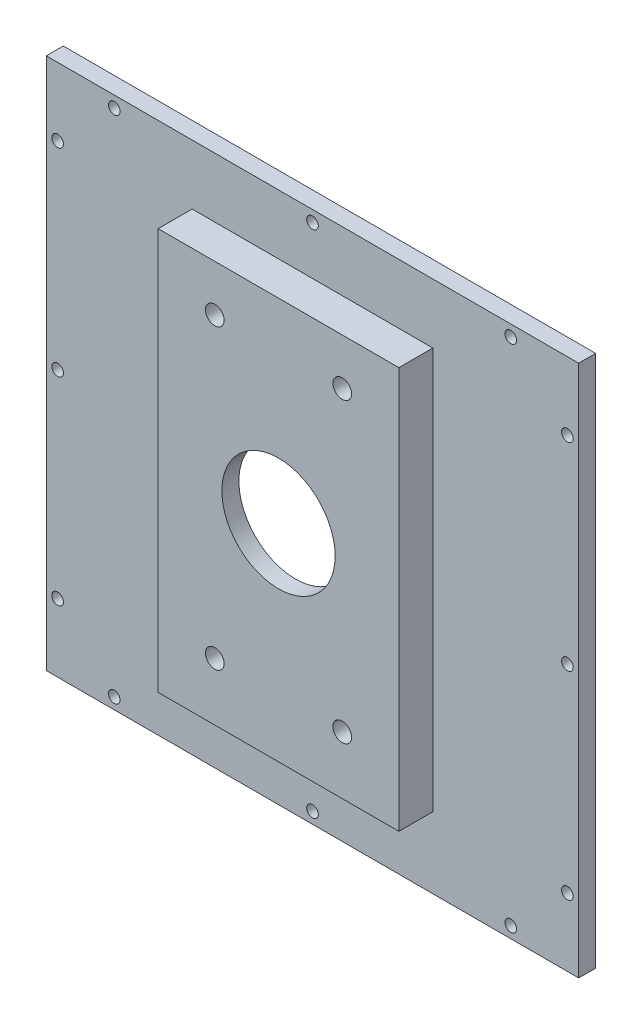
SolidWorks part; units mm, degrees
ref_plane "前视基准面" through (0, 0, 0) normal (0, 0, 1) x (1, 0, 0)
ref_plane "上视基准面" through (0, 0, 0) normal (0, 1, 0) x (1, 0, 0)
ref_plane "右视基准面" through (0, 0, 0) normal (1, 0, 0) x (0, 0, -1)
sketch "草图1" plane through (0, 0, 0) normal (0, 0, 1) x (1, 0, 0)
  line L0 (47, -49) -> (47, 45)
  line L1 (47, 45) -> (43, 45)
  line L2 (43, 45) -> (43, -49)
  line L3 (43, -49) -> (47, -49)
  line L4 (-43, -49) -> (43, -49)
  line L5 (43, -49) -> (43, -45)
  line L6 (43, -45) -> (-43, -45)
  line L7 (-43, -45) -> (-43, -49)
  line L8 (-43, -49) -> (-43, 45)
  line L9 (-43, 45) -> (-47, 45)
  line L10 (-47, 45) -> (-47, -49)
  line L11 (-47, -49) -> (-43, -49)
  line L12 (-43, 41) -> (43, 41)
  line L13 (43, 41) -> (43, 45)
  line L14 (43, 45) -> (26.5, 45)
  line L15 (26.5, 45) -> (-26.5, 45)
  line L16 (11.25, -36.45) -> (-11.25, -36.45)
  line L17 (11.25, 34.45) -> (-11.25, 34.45)
  line L18 (0, 45) -> (0, -49) construction
  line L19 (-11.25, 34.45) -> (-21.25, 34.45)
  line L20 (21.25, -36.45) -> (21.25, 34.45)
  line L21 (-11.25, -36.45) -> (-21.25, -36.45)
  line L22 (-26.5, 45) -> (-43, 45)
  line L23 (-43, 45) -> (-43, 41)
  line L24 (-21.25, -36.45) -> (-21.25, 34.45)
  line L25 (11.25, -36.45) -> (21.25, -36.45)
  line L26 (11.25, 34.45) -> (21.25, 34.45)
  line L27 (-10, 0) -> (10, 0) construction
  line L28 (-21.25, -30.45) -> (21.25, -30.45)
  line L29 (-21.25, 30.45) -> (21.25, 30.45)
  line L30 (-16.25, -36.45) -> (-16.25, 34.45)
  line L31 (16.25, 34.45) -> (16.25, -36.45)
  circle A0 centre (11.25, 26.25) radius 1.65
  circle A1 centre (11.25, -26.25) radius 1.65
  circle A2 centre (0, 0) radius 10
  circle A9 centre (-11.25, -26.25) radius 1.65
  circle A11 centre (11.25, -26.25) radius 1.65
  circle A13 centre (11.25, 26.25) radius 1.65
  circle A15 centre (-11.25, 26.25) radius 1.65
extrude "凸台-拉伸1" add sketch "草图1" along normal blind 3 contours L18 L12 L8 L6 L16 L21 L24 L19 L17 | L12 L18 L17 L26 L20 L25 L16 L6 L2 | L18 L15 L22 L8 L12 | L15 L18 L12 L2 L14 | L2 L3 L0 L1 | L10 L11 L7 L8 L9 | L18 L6 L7 L4 | L6 L18 L4 L2 region at (45, -2, 0) region at (0, -47, 0) region at (0, 43, 0) region at (0, -43.7838, 0) region at (-45, -2, 0)
extrude "凸台-拉伸2" add sketch "草图1<5>" along normal blind 6 contours L24 L20 L26 L17 L19 | L24 L21 L16 L25 L20 | L26 L31 L20 | L31 L20 | L31 L25 L20 | L21 L30 L24 | L30 L24 | L30 L19 L24 region at (0, -33.45, 0) region at (18.75, -33.45, 0) region at (-18.75, -33.45, 0) region at (18.75, 0, 0) region at (-18.75, 0, 0) region at (18.75, 32.45, 0) region at (0, 32.45, 0) region at (-18.75, 32.45, 0)
sketch "草图1<5>" plane through (0, 0, 0) normal (0, 0, 1) x (1, 0, 0) same geometry as "草图1"
ref_plane "基准面1" through (0, 0, 6) normal (0, 0, 1) x (1, 0, 0)
sketch "草图2" plane through (0, 0, 6) normal (0, 0, 1) x (1, 0, 0)
  line L16 (11.25, -36.45) -> (-11.25, -36.45)
  line L17 (11.25, 34.45) -> (-11.25, 34.45)
  line L18 (0, 45) -> (0, -49) construction
  line L19 (-11.25, 34.45) -> (-21.25, 34.45)
  line L20 (21.25, -36.45) -> (21.25, 34.45)
  line L21 (-11.25, -36.45) -> (-21.25, -36.45)
  line L24 (-21.25, -36.45) -> (-21.25, 34.45)
  line L25 (11.25, -36.45) -> (21.25, -36.45)
  line L26 (11.25, 34.45) -> (21.25, 34.45)
  circle A0 centre (11.25, 26.25) radius 1.65
  circle A1 centre (11.25, -26.25) radius 1.65
  circle A2 centre (0, 0) radius 10
  circle A9 centre (-11.25, -26.25) radius 1.65
  circle A11 centre (11.25, -26.25) radius 1.65
  circle A13 centre (11.25, 26.25) radius 1.65
  circle A15 centre (-11.25, 26.25) radius 1.65
extrude "凸台-拉伸3" add sketch "草图2" along normal blind 3 contours L18 L17 L19 L24 L21 L16 A2 A15 A9 | L17 L18 A2 L16 L25 L20 L26 A1 A0 | A0 | A15 | A1 | A9 region at (11.3692, -1.1307, 6) region at (-11.3692, -1.1307, 6) region at (11.25, 26.25, 6) region at (11.25, -26.25, 6) region at (-11.25, -26.25, 6) region at (-11.25, 26.25, 6)
hole_wizard "M4 螺纹孔1" positions "草图5" profile "草图6" tap size "M4" standard "GB"
sketch "草图5" plane through (0, 0, 9) normal (0, 0, 1) x (1, 0, 0)
  point P0 (11.25, 26.25)
  point P3 (-11.25, 26.25)
  point P6 (-11.25, -26.25)
  point P9 (11.25, -26.25)
sketch "草图6" plane through (11.25, 26.25, 9) normal (1, 0, 0) x (0, -1, 0)
  line L0 (0, 0) -> (0, 12.4914)
  line L1 (0, 12.4914) -> (1.65, 11.5)
  line L2 (1.65, 11.5) -> (1.65, 0)
  line L5 (1.65, 0) -> (0, 0)
  line L10 (0, 12.4914) -> (-1.65, 11.5) construction
  line L11 (0, -6.35) -> (0, 107.95) construction
  dimension "螺纹孔钻头直径" = 3.3
  dimension "螺纹孔钻头深度" = 11.5
  dimension "导头角度" = 118
cosmetic thread "孔螺蚊线1" parameters "D1"=3, "D2"=4
cosmetic thread "孔螺蚊线2" parameters "D1"=3, "D2"=4
cosmetic thread "孔螺蚊线3" parameters "D1"=3, "D2"=4
cosmetic thread "孔螺蚊线4" parameters "D1"=3, "D2"=4
sketch "草图7" plane through (0, 0, 0) normal (0, 0, 1) x (1, 0, 0)
  circle A0 centre (-45, -2) radius 1.25
  circle A1 centre (-45, 33) radius 1.25
  circle A2 centre (-45, -37) radius 1.25
  circle A3 centre (45, -2) radius 1.25
  circle A4 centre (45, 33) radius 1.25
  circle A5 centre (45, -37) radius 1.25
  circle A6 centre (0, -47) radius 1.25
  circle A7 centre (-35, -47) radius 1.25
  circle A8 centre (35, -47) radius 1.25
  circle A9 centre (0, 43) radius 1.25
  circle A10 centre (-35, 43) radius 1.25
  circle A11 centre (35, 43) radius 1.25
  dimension "D1" = 2
  dimension "D2" = 2
hole_wizard "M2.5 螺纹孔1" positions "草图8" profile "草图9" tap size "M2.5" standard "GB"
sketch "草图8" plane through (0, 0, 3) normal (0, 0, 1) x (1, 0, 0)
  point P0 (-45, 33)
  point P3 (-45, -2)
  point P6 (-45, -37)
  point P10 (-35, 43)
  point P13 (0, 43)
  point P16 (35, 43)
  point P19 (45, 33)
sketch "草图9" plane through (-45, 33, 3) normal (1, 0, 0) x (0, -1, 0)
  line L0 (0, 0) -> (0, 7.8659)
  line L1 (0, 7.8659) -> (1.025, 7.25)
  line L2 (1.025, 7.25) -> (1.025, 0)
  line L5 (1.025, 0) -> (0, 0)
  line L10 (0, 7.8659) -> (-1.025, 7.25) construction
  line L11 (0, -6.35) -> (0, 107.95) construction
  dimension "螺纹孔钻头直径" = 2.05
  dimension "螺纹孔钻头深度" = 7.25
  dimension "导头角度" = 118
cosmetic thread "孔螺蚊线5" parameters "D1"=3, "D2"=2.5
cosmetic thread "孔螺蚊线6" parameters "D1"=3, "D2"=2.5
cosmetic thread "孔螺蚊线7" parameters "D1"=3, "D2"=2.5
cosmetic thread "孔螺蚊线8" parameters "D1"=3, "D2"=2.5
cosmetic thread "孔螺蚊线9" parameters "D1"=3, "D2"=2.5
cosmetic thread "孔螺蚊线10" parameters "D1"=3, "D2"=2.5
cosmetic thread "孔螺蚊线11" parameters "D1"=3, "D2"=2.5
hole_wizard "M2.5 螺纹孔2" positions "草图12" profile "草图13" tap size "M2.5" standard "GB"
sketch "草图12" plane through (0, 0, 3) normal (0, 0, 1) x (1, 0, 0)
  point P0 (45, -2)
  point P3 (45, -37)
  point P6 (35, -47)
  point P9 (0, -47)
  point P12 (-35, -47)
sketch "草图13" plane through (45, -2, 3) normal (1, 0, 0) x (0, -1, 0)
  line L0 (0, 0) -> (0, 7.8659)
  line L1 (0, 7.8659) -> (1.025, 7.25)
  line L2 (1.025, 7.25) -> (1.025, 0)
  line L5 (1.025, 0) -> (0, 0)
  line L10 (0, 7.8659) -> (-1.025, 7.25) construction
  line L11 (0, -6.35) -> (0, 107.95) construction
  dimension "螺纹孔钻头直径" = 2.05
  dimension "螺纹孔钻头深度" = 7.25
  dimension "导头角度" = 118
cosmetic thread "孔螺蚊线12" parameters "D1"=3, "D2"=2.5
cosmetic thread "孔螺蚊线13" parameters "D1"=3, "D2"=2.5
cosmetic thread "孔螺蚊线14" parameters "D1"=3, "D2"=2.5
cosmetic thread "孔螺蚊线15" parameters "D1"=3, "D2"=2.5
cosmetic thread "孔螺蚊线16" parameters "D1"=3, "D2"=2.5
